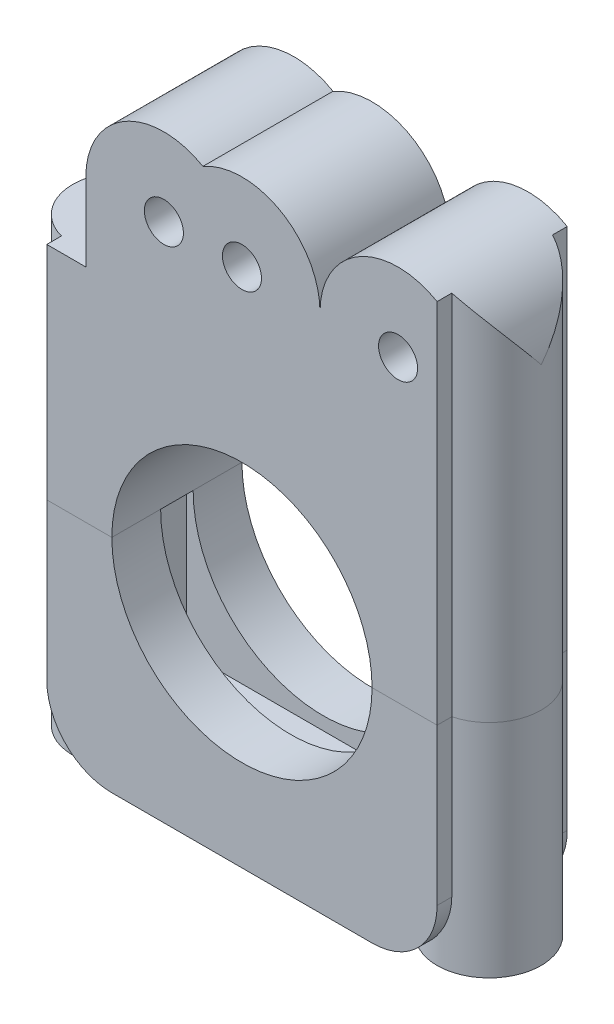
SolidWorks part; units mm, degrees
material "ABS"
ref_plane "Front Plane" through (0, 0, 0) normal (0, 0, 1) x (1, 0, 0)
ref_plane "Top Plane" through (0, 0, 0) normal (0, 1, 0) x (1, 0, 0)
ref_plane "Right Plane" through (0, 0, 0) normal (1, 0, 0) x (0, 0, -1)
sketch "Sketch1" plane through (0, 0, 0) normal (0, 0, 1) x (1, 0, 0)
  line L0 (-6, 23) -> (12, 23) construction
  line L1 (-18, -17) -> (18, -17)
  line L2 (-18, -17) -> (-18, 17)
  line L3 (-18, 17) -> (18, 17)
  line L4 (18, -17) -> (18, 17)
  line L5 (-18, -17) -> (18, 17) construction
  line L6 (-18, 17) -> (18, -17) construction
  line L7 (18, 17) -> (18, 23)
  line L8 (-12, 23) -> (-12, 17)
  circle A0 centre (0, 0) radius 10
  circle A1 centre (-6, 23) radius 1.5
  circle A2 centre (0, 23) radius 1.5
  circle A3 centre (12, 23) radius 1.5
  circle A4 centre (-6, 23) radius 6
  circle A5 centre (0, 23) radius 6
  circle A6 centre (12, 23) radius 6
  dimension "D1" = 20
  dimension "D4" = 6
  dimension "D5" = 3
  dimension "D6" = 3
  dimension "D7" = 3
  dimension "D11" = 12
  dimension "D2" = 34
  dimension "D3" = 36
  dimension "D12" = 23
  dimension "D13" = 6
  dimension "D8" = 4.5
  dimension "D9" = 4.5
  dimension "D10" = 4.5
extrude "Boss-Extrude1" add sketch "Sketch1" along normal blind 10 contours L1 L4 L3 L2 A0 | A5 A4 A1 | A4 L8 L3 | A4 A5 A1 A2 | A6 A3 | A5 A4 L3 | A6 A5 L3 | A4 A5 A2 | A6 L3 L7 region at (-17.5048, 0, 0) region at (16.6598, 18.3402, 0) region at (-10.6598, 18.3402, 0) region at (6, 18.3402, 0) region at (7.8774, 18.8774, 0) region at (-3, 17.2381, 0) region at (-8.0018, 23, 0) region at (2.0018, 23, 0) region at (-3, 23, 0)
sketch "Sketch2" plane through (0, -17, 0) normal (0, -1, 0) x (1, 0, 0)
  line L0 (-18, 5) -> (18, 5) construction
  line L2 (18, 10) -> (18, 0) construction
  line L3 (0, 0) -> (0, 10) construction
  line L4 (-18, 10) -> (18, 10) construction
  line L5 (-14, 5) -> (-18, 5) construction
  line L6 (-18, 10) -> (-18, 0) construction
  line L7 (-14, 0) -> (-14, 10)
  line L8 (-18, 0) -> (18, 0) construction
  line L9 (-15, 10) -> (-15, 0)
  line L10 (14, 0) -> (14, 10)
  line L11 (15, 10) -> (15, 0)
  circle A2 centre (-14, 5) radius 4
  circle A3 centre (-14, 5) radius 2
  circle A4 centre (14, 5) radius 2
  circle A5 centre (14, 5) radius 4
  line M7 (-18, 0) -> (18, 0)
  line M8 (18, 0) -> (18, 10)
  line M9 (18, 10) -> (-18, 10)
  line M10 (-18, 10) -> (-18, 0)
  dimension "D1" = 8
  dimension "D3" = 3
  dimension "D2" = 4
extrude "Cut-Extrude1" cut sketch "Sketch2" against normal up to surface (34 mm away) contours L7 A3 | L7 A3 L9 | L9 A3 | A4 L11 | A4 L10 L11 | A4 L10 | L11 A5 M8 M9 | A5 L11 M8 M7 | A2 L9 M9 M10 | A2 L9 M10 M7 region at (-16.8373, -17, 1.245) region at (-14.4885, -17, 5) region at (-13.1512, -17, 5) region at (16.8373, -17, 1.245) region at (-15.41, -17, 5) region at (-16.8373, -17, 8.755) region at (13.1512, -17, 5) region at (14.4885, -17, 5) region at (15.41, -17, 5) region at (16.8373, -17, 8.755) up to face at (-15, 17, 5)
extrude "Cut-Extrude2" cut sketch "Sketch2<3>" against normal through all contours L11 A5 M8 M9 | A5 L11 M8 M7 region at (16.8373, -17, 1.245) region at (16.8373, -17, 8.755)
sketch "Sketch2<3>" plane through (0, -17, 0) normal (0, -1, 0) x (1, 0, 0) same geometry as "Sketch2"
ref_plane "Plane1" through (0, -10, 0) normal (0, 1, 0) x (1, 0, 0)
sketch "Sketch3" plane through (0, -10, 0) normal (0, 1, 0) x (1, 0, 0)
  line L0 (10, 0) -> (-10, 0) construction
  line L1 (-10, 0) -> (10, 0)
  line L2 (-10, 0) -> (-10, -10)
  line L3 (-10, -10) -> (10, -10)
  line L4 (10, 0) -> (10, -10)
  line L5 (-10, 0) -> (-10, -10) construction
  line L6 (10, -10) -> (10, 0) construction
  line L7 (-10, -10) -> (10, -10) construction
  line L8 (-8.6621, -3.75) -> (-8.6621, -6.25) construction
  line L9 (-10, -6.25) -> (10, -6.25)
  line L10 (-10, -6.25) -> (-10, -3.75)
  line L11 (-10, -3.75) -> (10, -3.75)
  line L12 (10, -6.25) -> (10, -3.75)
  line L14 (-10, -3.75) -> (-10.5, -3.75)
  line L15 (-10, -3.75) -> (-10, -6.25)
  line L16 (-10, -6.25) -> (-10.5, -6.25)
  line L17 (-10.5, -3.75) -> (-10.5, -6.25)
  line L18 (10, -6.25) -> (10.5, -6.25)
  line L19 (10, -6.25) -> (10, -3.75)
  line L20 (10, -3.75) -> (10.5, -3.75)
  line L21 (10.5, -6.25) -> (10.5, -3.75)
  point P18 (-8.6621, -5)
  point P19 (-10, -5)
  dimension "D1" = 2.5
  dimension "D2" = 0
  dimension "D3" = 0.5
  dimension "D4" = 0.5
extrude "Cut-Extrude3" cut sketch "Sketch3" along normal blind 10 contours L11 L8 L9 L4 | L8 L11 L2 L9 | L14 L17 L16 L2 | L18 L21 L20 L4 region at (-9.3311, -10, 5) region at (-10.25, -10, 5) region at (10.25, -10, 5) region at (0.6689, -10, 5)
extrude "Cut-Extrude4" cut sketch "Sketch3<3>" against normal blind 1 contours L11 L8 L9 L4 | L8 L11 L2 L9 | L14 L17 L16 L2 | L18 L21 L20 L4 region at (-9.3311, -10, 5) region at (-10.25, -10, 5) region at (10.25, -10, 5) region at (0.6689, -10, 5)
sketch "Sketch3<3>" plane through (0, -10, 0) normal (0, 1, 0) x (1, 0, 0) same geometry as "Sketch3"
fillet "Fillet1" radius 5 4 edges at (15, -17, 9.4365) (15, -17, 0.5635) (-15, -17, 9.4365) (-15, -17, 0.5635)
chamfer "Chamfer1" distance 1.5 angle 45 2 edges at (14, -17, 3) (-14, -17, 3)
ref_plane "Plane2" through (0, 0, 0) normal (0, 1, 0) x (1, 0, 0)
split "Split1" trim tools "Plane2" bodies to split 105 resulting bodies 107 108
